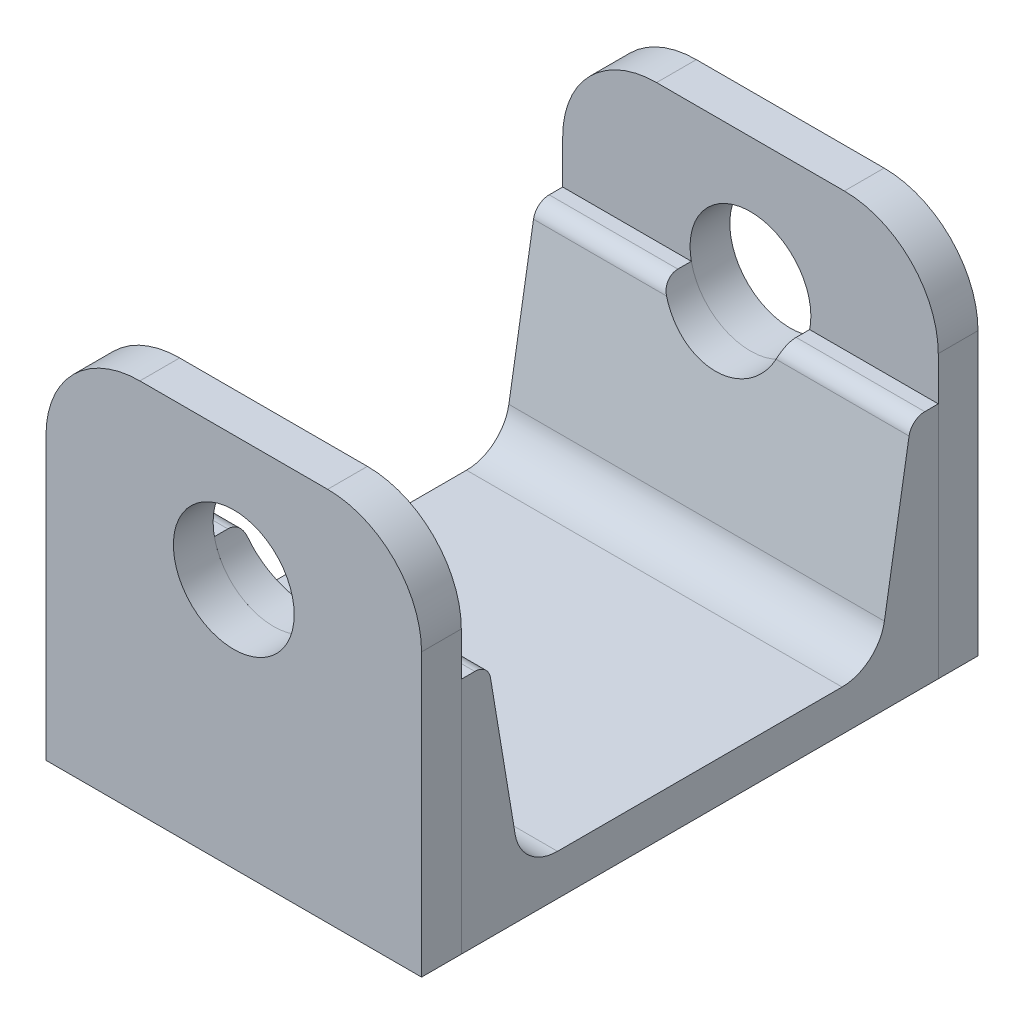
SolidWorks part; units mm, degrees
other "Elemento de detalle1"
other "Elemento de detalle2"
other "Carpeta de soldadura"
other "Cordón de soldadura1"
other "Cordón de soldadura2"
material "AISI 1010 Barra de acero laminada en caliente"
ref_plane "Alzado" through (0, 0, 0) normal (0, 0, 1) x (1, 0, 0)
ref_plane "Planta" through (0, 0, 0) normal (0, 1, 0) x (1, 0, 0)
ref_plane "Vista lateral" through (0, 0, 0) normal (1, 0, 0) x (0, 0, -1)
sketch "Croquis1" plane through (0, 0, 0) normal (0, 0, 1) x (1, 0, 0)
  line L0 (-18.5367, 0) -> (41.4633, 0)
  dimension "D1" = 60
other "Miembro estructural1"
ref_plane "Plano1" through (-18.5367, 0, 0) normal (1, 0, 0) x (0, 1, 0)
sketch "Sketch1" plane through (-18.5367, 0, 0) normal (1, 0, 0) x (0, 1, 0)
  line L0 (0, -38.1) -> (0, 38.1)
  line L1 (0, 38.1) -> (38.0492, 38.1)
  line L2 (0, -38.1) -> (38.0492, -38.1)
  line L5 (31.75, -31.1658) -> (6.35, -31.1658) construction
  line L6 (0, 0) -> (6.5532, 0) construction
  line L12 (6.5532, 22.7314) -> (6.5532, -22.7314)
  line L15 (38.0492, 38.1) -> (38.0492, 35.9423)
  line L16 (38.0492, -38.1) -> (38.0492, -35.9423)
  line L17 (12.2837, 29.4961) -> (35.9268, 33.4369)
  line L18 (12.2837, -29.4961) -> (35.9268, -33.4369)
  arc A9 (6.5532, -22.7314) -> (12.2837, -29.4961) centre (13.4112, -22.7314) ccw
  arc A10 (6.5532, 22.7314) -> (12.2837, 29.4961) centre (13.4112, 22.7314) cw
  arc A11 (38.0492, 35.9423) -> (35.9268, 33.4369) centre (35.5092, 35.9423) cw
  arc A12 (38.0492, -35.9423) -> (35.9268, -33.4369) centre (35.5092, -35.9423) ccw
  point P4 (38.0492, 33.7907)
  point P5 (38.0492, -33.7907)
  point P6 (3.2766, 0)
  point P7 (19.0246, 38.1)
  point P12 (19.0246, -38.1)
  point P13 (0, 0)
  dimension "RI" = 6.858
  dimension "D2" = 9.463
  dimension "RA" = 2.54
  dimension "Depth" = 76.2
  dimension "BF" = 38.0492
  dimension "TW" = 6.5532
  dimension "flange" = 2.1577
  dimension "TF" = 6.9342
sketch "Croquis19" plane through (0, 0, 38.1) normal (0, 0, 1) x (1, 0, 0)
  line L0 (41.4633, 38.0492) -> (41.4633, 0) construction
  line L1 (-18.5367, 0) -> (41.4633, 0)
  line L2 (-18.5367, 0) -> (-18.5367, 60)
  line L3 (-18.5367, 60) -> (41.4633, 60)
  line L4 (41.4633, 0) -> (41.4633, 60)
  dimension "D1" = 60
sketch "Croquis20" plane through (0, 0, -38.1) normal (0, 0, -1) x (-1, 0, 0)
  line L0 (18.5367, 0) -> (18.5367, 38.0492) construction
  line L1 (-41.4633, 0) -> (18.5367, 0)
  line L2 (-41.4633, 0) -> (-41.4633, 60)
  line L3 (-41.4633, 60) -> (18.5367, 60)
  line L4 (18.5367, 0) -> (18.5367, 60)
  dimension "D1" = 60
base flange "Brida base2" sketch "Croquis20" thickness 6.35 reverse thickness direction yes parameters "D1"=0.7366
base flange "Brida base3" sketch "Croquis19" thickness 6.35 reverse thickness direction yes parameters "D1"=0.7366
sketch "Croquis4" plane through (0, 0, 38.1) normal (0, 0, 1) x (1, 0, 0)
  line L1 (41.4633, 60) -> (-18.5367, 60) construction
  line L2 (11.4633, 60) -> (11.4633, 9.9981) construction
  line L3 (41.4633, 60) -> (-18.5367, 60) construction
  circle A0 centre (11.4633, 40) radius 9.65
  dimension "D1" = 19.3
  dimension "D2" = 20
extrude "Cortar-Extruir1" cut sketch "Croquis4" against normal through all both and the other way through all
fillet "Redondeo1" radius 15
fillet "Redondeo2" radius 15
ref_plane "Plano2" through (11.4633, 0, 0) normal (1, 0, 0) x (0, 0, -1)
sketch "Líneas de pliegue3" [suppressed] plane through (0, 0, 0) normal (0, 1, 0) x (1, 0, 0)
sketch "Cuadro delimitador3" [suppressed] plane through (0, 0, 0) normal (0, 1, 0) x (1, 0, 0)
sheet metal parameters "Chapa metálica4" thickness 6.35 parameters "D1"=0.7366
flat pattern "Chapa desplegada4" [suppressed]
sketch "Líneas de pliegue4" plane through (0, 0, 0) normal (0, 1, 0) x (1, 0, 0)
sketch3d "Cuadro delimitador4" [suppressed]
  line L0 (18.5367, 60, 0) -> (18.5367, 0, 0) construction
  line L1 (-21.4633, 60, 0) -> (-21.4633, 0, 0) construction
  line L2 (18.5367, 60, 0) -> (-21.4633, 60, 0) construction
  line L3 (18.5367, 0, 0) -> (-21.4633, 0, 0) construction
sheet metal parameters "Chapa metálica5" thickness 6.35 parameters "D1"=0.7366
flat pattern "Chapa desplegada5"
sketch "Líneas de pliegue5" plane through (0, 0, 0) normal (0, 1, 0) x (1, 0, 0)
sketch "Cuadro delimitador5" [suppressed] plane through (0, 0, 0) normal (0, 1, 0) x (1, 0, 0)
sheet metal parameters "Chapa metálica7" thickness 6.35 parameters "D1"=0.7366
flat pattern "Chapa desplegada4"
sketch "Líneas de pliegue4" plane through (0, 0, 0) normal (0, 1, 0) x (1, 0, 0)
sketch3d "Cuadro delimitador4" [suppressed]
  line L0 (-18.5367, 0, 0) -> (41.4633, 0, 0) construction
  line L1 (-18.5367, 60, 0) -> (41.4633, 60, 0) construction
  line L2 (-18.5367, 0, 0) -> (-18.5367, 60, 0) construction
  line L3 (41.4633, 0, 0) -> (41.4633, 60, 0) construction
sheet metal parameters "Chapa metálica8" thickness 6.35 parameters "D1"=0.7366
flat pattern "Chapa desplegada5"
sketch "Líneas de pliegue5" plane through (0, 0, 0) normal (0, 1, 0) x (1, 0, 0)
sketch3d "Cuadro delimitador5" [suppressed]
  line L0 (-21.4633, 0, 0) -> (-21.4633, 60, 0) construction
  line L1 (18.5367, 0, 0) -> (18.5367, 60, 0) construction
  line L2 (-21.4633, 0, 0) -> (18.5367, 0, 0) construction
  line L3 (-21.4633, 60, 0) -> (18.5367, 60, 0) construction
